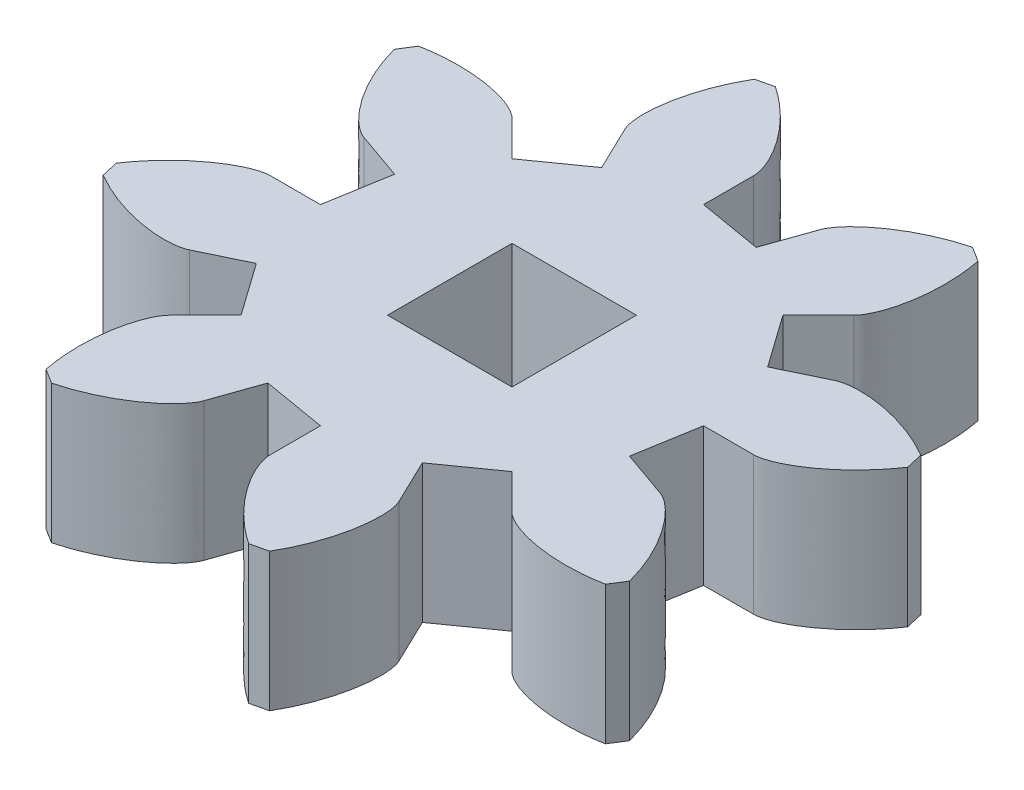
SolidWorks part; units mm, degrees
ref_plane "Front Plane" through (0, 0, 0) normal (0, 0, 1) x (1, 0, 0)
ref_plane "Top Plane" through (0, 0, 0) normal (0, 1, 0) x (1, 0, 0)
ref_plane "Right Plane" through (0, 0, 0) normal (1, 0, 0) x (0, 0, -1)
sketch "Sketch2" plane through (0, 0, 0) normal (0, 1, 0) x (1, 0, 0)
  circle A0 centre (0, 0) radius 5.8346 construction
  circle A1 centre (0, 0) radius 5.8346
sketch "Sketch3" plane through (0, 0, 0) normal (0, 1, 0) x (1, 0, 0)
  line L0 (4.157, 0) -> (5.2447, 0)
  line L1 (5.2447, 0) -> (5.2537, 0.0004)
  line L2 (5.2537, 0.0004) -> (5.2726, 0.002)
  line L3 (5.2726, 0.002) -> (5.3013, 0.0057)
  line L4 (5.3013, 0.0057) -> (5.3397, 0.0123)
  line L5 (5.3397, 0.0123) -> (5.3875, 0.0227)
  line L6 (5.3875, 0.0227) -> (5.4444, 0.0378)
  line L7 (5.4444, 0.0378) -> (5.5102, 0.0582)
  line L8 (5.5102, 0.0582) -> (5.5844, 0.0849)
  line L9 (5.5844, 0.0849) -> (5.6666, 0.1186)
  line L10 (5.6666, 0.1186) -> (5.7563, 0.16)
  line L11 (5.7563, 0.16) -> (5.8531, 0.2099)
  line L12 (5.8531, 0.2099) -> (5.9562, 0.2688)
  line L13 (5.9562, 0.2688) -> (6.0651, 0.3376)
  line L14 (6.0651, 0.3376) -> (6.1791, 0.4167)
  line L15 (6.1791, 0.4167) -> (6.2974, 0.5068)
  line L16 (6.2974, 0.5068) -> (6.4195, 0.6083)
  line L17 (6.4195, 0.6083) -> (6.5443, 0.7218)
  line L18 (6.5443, 0.7218) -> (6.6712, 0.8476)
  line L19 (6.6712, 0.8476) -> (6.7992, 0.9862)
  line L20 (6.7992, 0.9862) -> (6.9276, 1.1378)
  line L21 (6.9276, 1.1378) -> (7.0553, 1.3028)
  line L22 (7.0553, 1.3028) -> (7.1186, 1.3904)
  line L23 (7.1186, 1.3904) -> (7.1501, 1.4354)
  line L24 (7.1501, 1.4354) -> (7.1502, 1.4358)
  line L25 (7.1502, 1.4358) -> (7.0661, 1.8051)
  line L26 (7.0661, 1.8051) -> (7.0658, 1.8053)
  line L27 (7.0658, 1.8053) -> (7.0179, 1.8323)
  line L28 (7.0179, 1.8323) -> (6.9228, 1.8838)
  line L29 (6.9228, 1.8838) -> (6.7362, 1.9771)
  line L30 (6.7362, 1.9771) -> (6.5549, 2.0582)
  line L31 (6.5549, 2.0582) -> (6.3794, 2.1275)
  line L32 (6.3794, 2.1275) -> (6.2105, 2.1859)
  line L33 (6.2105, 2.1859) -> (6.0488, 2.2341)
  line L34 (6.0488, 2.2341) -> (5.8949, 2.2727)
  line L35 (5.8949, 2.2727) -> (5.7492, 2.3025)
  line L36 (5.7492, 2.3025) -> (5.6121, 2.3244)
  line L37 (5.6121, 2.3244) -> (5.4842, 2.3392)
  line L38 (5.4842, 2.3392) -> (5.3657, 2.3477)
  line L39 (5.3657, 2.3477) -> (5.2569, 2.3507)
  line L40 (5.2569, 2.3507) -> (5.1581, 2.3491)
  line L41 (5.1581, 2.3491) -> (5.0694, 2.3438)
  line L42 (5.0694, 2.3438) -> (4.991, 2.3357)
  line L43 (4.991, 2.3357) -> (4.9228, 2.3256)
  line L44 (4.9228, 2.3256) -> (4.865, 2.3145)
  line L45 (4.865, 2.3145) -> (4.8174, 2.3032)
  line L46 (4.8174, 2.3032) -> (4.78, 2.2925)
  line L47 (4.78, 2.2925) -> (4.7525, 2.2834)
  line L48 (4.7525, 2.2834) -> (4.7348, 2.2767)
  line L49 (4.7348, 2.2767) -> (4.7265, 2.2731)
  line L50 (4.7265, 2.2731) -> (3.7463, 1.8017)
  line L51 (3.7463, 1.8017) -> (2.9394, 2.9394)
  line L52 (2.9394, 2.9394) -> (3.7086, 3.7086)
  line L53 (3.7086, 3.7086) -> (3.7146, 3.7152)
  line L54 (3.7146, 3.7152) -> (3.7269, 3.7297)
  line L55 (3.7269, 3.7297) -> (3.7446, 3.7526)
  line L56 (3.7446, 3.7526) -> (3.767, 3.7844)
  line L57 (3.767, 3.7844) -> (3.7934, 3.8256)
  line L58 (3.7934, 3.8256) -> (3.8231, 3.8765)
  line L59 (3.8231, 3.8765) -> (3.8551, 3.9375)
  line L60 (3.8551, 3.9375) -> (3.8887, 4.0088)
  line L61 (3.8887, 4.0088) -> (3.923, 4.0908)
  line L62 (3.923, 4.0908) -> (3.9572, 4.1835)
  line L63 (3.9572, 4.1835) -> (3.9904, 4.2871)
  line L64 (3.9904, 4.2871) -> (4.0216, 4.4018)
  line L65 (4.0216, 4.4018) -> (4.05, 4.5274)
  line L66 (4.05, 4.5274) -> (4.0746, 4.6639)
  line L67 (4.0746, 4.6639) -> (4.0946, 4.8113)
  line L68 (4.0946, 4.8113) -> (4.1091, 4.9694)
  line L69 (4.1091, 4.9694) -> (4.1172, 5.1379)
  line L70 (4.1172, 5.1379) -> (4.1179, 5.3166)
  line L71 (4.1179, 5.3166) -> (4.1105, 5.5051)
  line L72 (4.1105, 5.5051) -> (4.094, 5.7031)
  line L73 (4.094, 5.7031) -> (4.0676, 5.9101)
  line L74 (4.0676, 5.9101) -> (4.0505, 6.0168)
  line L75 (4.0505, 6.0168) -> (4.0409, 6.0709)
  line L76 (4.0409, 6.0709) -> (4.0407, 6.0712)
  line L77 (4.0407, 6.0712) -> (3.7201, 6.2728)
  line L78 (3.7201, 6.2728) -> (3.7197, 6.2728)
  line L79 (3.7197, 6.2728) -> (3.6668, 6.258)
  line L80 (3.6668, 6.258) -> (3.5632, 6.2272)
  line L81 (3.5632, 6.2272) -> (3.3652, 6.1613)
  line L82 (3.3652, 6.1613) -> (3.1797, 6.0903)
  line L83 (3.1797, 6.0903) -> (3.0065, 6.0153)
  line L84 (3.0065, 6.0153) -> (2.8458, 5.9372)
  line L85 (2.8458, 5.9372) -> (2.6974, 5.8569)
  line L86 (2.6974, 5.8569) -> (2.5613, 5.7753)
  line L87 (2.5613, 5.7753) -> (2.4371, 5.6934)
  line L88 (2.4371, 5.6934) -> (2.3247, 5.612)
  line L89 (2.3247, 5.612) -> (2.2238, 5.532)
  line L90 (2.2238, 5.532) -> (2.1341, 5.4542)
  line L91 (2.1341, 5.4542) -> (2.055, 5.3794)
  line L92 (2.055, 5.3794) -> (1.9863, 5.3084)
  line L93 (1.9863, 5.3084) -> (1.9273, 5.242)
  line L94 (1.9273, 5.242) -> (1.8776, 5.1807)
  line L95 (1.8776, 5.1807) -> (1.8365, 5.1254)
  line L96 (1.8365, 5.1254) -> (1.8035, 5.0767)
  line L97 (1.8035, 5.0767) -> (1.7778, 5.035)
  line L98 (1.7778, 5.035) -> (1.7589, 5.001)
  line L99 (1.7589, 5.001) -> (1.7459, 4.9751)
  line L100 (1.7459, 4.9751) -> (1.7382, 4.9578)
  line L101 (1.7382, 4.9578) -> (1.7348, 4.9495)
  line L102 (1.7348, 4.9495) -> (1.375, 3.923)
  line L103 (1.375, 3.923) -> (0, 4.157)
  line L104 (0, 4.157) -> (0, 5.2447)
  line L105 (0, 5.2447) -> (-0.0004, 5.2537)
  line L106 (-0.0004, 5.2537) -> (-0.002, 5.2726)
  line L107 (-0.002, 5.2726) -> (-0.0057, 5.3013)
  line L108 (-0.0057, 5.3013) -> (-0.0123, 5.3397)
  line L109 (-0.0123, 5.3397) -> (-0.0227, 5.3875)
  line L110 (-0.0227, 5.3875) -> (-0.0378, 5.4444)
  line L111 (-0.0378, 5.4444) -> (-0.0582, 5.5102)
  line L112 (-0.0582, 5.5102) -> (-0.0849, 5.5844)
  line L113 (-0.0849, 5.5844) -> (-0.1186, 5.6666)
  line L114 (-0.1186, 5.6666) -> (-0.16, 5.7563)
  line L115 (-0.16, 5.7563) -> (-0.2099, 5.8531)
  line L116 (-0.2099, 5.8531) -> (-0.2688, 5.9562)
  line L117 (-0.2688, 5.9562) -> (-0.3376, 6.0651)
  line L118 (-0.3376, 6.0651) -> (-0.4167, 6.1791)
  line L119 (-0.4167, 6.1791) -> (-0.5068, 6.2974)
  line L120 (-0.5068, 6.2974) -> (-0.6083, 6.4195)
  line L121 (-0.6083, 6.4195) -> (-0.7218, 6.5443)
  line L122 (-0.7218, 6.5443) -> (-0.8476, 6.6712)
  line L123 (-0.8476, 6.6712) -> (-0.9862, 6.7992)
  line L124 (-0.9862, 6.7992) -> (-1.1378, 6.9276)
  line L125 (-1.1378, 6.9276) -> (-1.3028, 7.0553)
  line L126 (-1.3028, 7.0553) -> (-1.3904, 7.1186)
  line L127 (-1.3904, 7.1186) -> (-1.4354, 7.1501)
  line L128 (-1.4354, 7.1501) -> (-1.4358, 7.1502)
  line L129 (-1.4358, 7.1502) -> (-1.8051, 7.0661)
  line L130 (-1.8051, 7.0661) -> (-1.8053, 7.0658)
  line L131 (-1.8053, 7.0658) -> (-1.8323, 7.0179)
  line L132 (-1.8323, 7.0179) -> (-1.8838, 6.9228)
  line L133 (-1.8838, 6.9228) -> (-1.9771, 6.7362)
  line L134 (-1.9771, 6.7362) -> (-2.0582, 6.5549)
  line L135 (-2.0582, 6.5549) -> (-2.1275, 6.3794)
  line L136 (-2.1275, 6.3794) -> (-2.1859, 6.2105)
  line L137 (-2.1859, 6.2105) -> (-2.2341, 6.0488)
  line L138 (-2.2341, 6.0488) -> (-2.2727, 5.8949)
  line L139 (-2.2727, 5.8949) -> (-2.3025, 5.7492)
  line L140 (-2.3025, 5.7492) -> (-2.3244, 5.6121)
  line L141 (-2.3244, 5.6121) -> (-2.3392, 5.4842)
  line L142 (-2.3392, 5.4842) -> (-2.3477, 5.3657)
  line L143 (-2.3477, 5.3657) -> (-2.3507, 5.2569)
  line L144 (-2.3507, 5.2569) -> (-2.3491, 5.1581)
  line L145 (-2.3491, 5.1581) -> (-2.3438, 5.0694)
  line L146 (-2.3438, 5.0694) -> (-2.3357, 4.991)
  line L147 (-2.3357, 4.991) -> (-2.3256, 4.9228)
  line L148 (-2.3256, 4.9228) -> (-2.3145, 4.865)
  line L149 (-2.3145, 4.865) -> (-2.3032, 4.8174)
  line L150 (-2.3032, 4.8174) -> (-2.2925, 4.78)
  line L151 (-2.2925, 4.78) -> (-2.2834, 4.7525)
  line L152 (-2.2834, 4.7525) -> (-2.2767, 4.7348)
  line L153 (-2.2767, 4.7348) -> (-2.2731, 4.7265)
  line L154 (-2.2731, 4.7265) -> (-1.8017, 3.7463)
  line L155 (-1.8017, 3.7463) -> (-2.9394, 2.9394)
  line L156 (-2.9394, 2.9394) -> (-3.7086, 3.7086)
  line L157 (-3.7086, 3.7086) -> (-3.7152, 3.7146)
  line L158 (-3.7152, 3.7146) -> (-3.7297, 3.7269)
  line L159 (-3.7297, 3.7269) -> (-3.7526, 3.7446)
  line L160 (-3.7526, 3.7446) -> (-3.7844, 3.767)
  line L161 (-3.7844, 3.767) -> (-3.8256, 3.7934)
  line L162 (-3.8256, 3.7934) -> (-3.8765, 3.8231)
  line L163 (-3.8765, 3.8231) -> (-3.9375, 3.8551)
  line L164 (-3.9375, 3.8551) -> (-4.0088, 3.8887)
  line L165 (-4.0088, 3.8887) -> (-4.0908, 3.923)
  line L166 (-4.0908, 3.923) -> (-4.1835, 3.9572)
  line L167 (-4.1835, 3.9572) -> (-4.2871, 3.9904)
  line L168 (-4.2871, 3.9904) -> (-4.4018, 4.0216)
  line L169 (-4.4018, 4.0216) -> (-4.5274, 4.05)
  line L170 (-4.5274, 4.05) -> (-4.6639, 4.0746)
  line L171 (-4.6639, 4.0746) -> (-4.8113, 4.0946)
  line L172 (-4.8113, 4.0946) -> (-4.9694, 4.1091)
  line L173 (-4.9694, 4.1091) -> (-5.1379, 4.1172)
  line L174 (-5.1379, 4.1172) -> (-5.3166, 4.1179)
  line L175 (-5.3166, 4.1179) -> (-5.5051, 4.1105)
  line L176 (-5.5051, 4.1105) -> (-5.7031, 4.094)
  line L177 (-5.7031, 4.094) -> (-5.9101, 4.0676)
  line L178 (-5.9101, 4.0676) -> (-6.0168, 4.0505)
  line L179 (-6.0168, 4.0505) -> (-6.0709, 4.0409)
  line L180 (-6.0709, 4.0409) -> (-6.0712, 4.0407)
  line L181 (-6.0712, 4.0407) -> (-6.2728, 3.7201)
  line L182 (-6.2728, 3.7201) -> (-6.2728, 3.7197)
  line L183 (-6.2728, 3.7197) -> (-6.258, 3.6668)
  line L184 (-6.258, 3.6668) -> (-6.2272, 3.5632)
  line L185 (-6.2272, 3.5632) -> (-6.1613, 3.3652)
  line L186 (-6.1613, 3.3652) -> (-6.0903, 3.1797)
  line L187 (-6.0903, 3.1797) -> (-6.0153, 3.0065)
  line L188 (-6.0153, 3.0065) -> (-5.9372, 2.8458)
  line L189 (-5.9372, 2.8458) -> (-5.8569, 2.6974)
  line L190 (-5.8569, 2.6974) -> (-5.7753, 2.5613)
  line L191 (-5.7753, 2.5613) -> (-5.6934, 2.4371)
  line L192 (-5.6934, 2.4371) -> (-5.612, 2.3247)
  line L193 (-5.612, 2.3247) -> (-5.532, 2.2238)
  line L194 (-5.532, 2.2238) -> (-5.4542, 2.1341)
  line L195 (-5.4542, 2.1341) -> (-5.3794, 2.055)
  line L196 (-5.3794, 2.055) -> (-5.3084, 1.9863)
  line L197 (-5.3084, 1.9863) -> (-5.242, 1.9273)
  line L198 (-5.242, 1.9273) -> (-5.1807, 1.8776)
  line L199 (-5.1807, 1.8776) -> (-5.1254, 1.8365)
  line L200 (-5.1254, 1.8365) -> (-5.0767, 1.8035)
  line L201 (-5.0767, 1.8035) -> (-5.035, 1.7778)
  line L202 (-5.035, 1.7778) -> (-5.001, 1.7589)
  line L203 (-5.001, 1.7589) -> (-4.9751, 1.7459)
  line L204 (-4.9751, 1.7459) -> (-4.9578, 1.7382)
  line L205 (-4.9578, 1.7382) -> (-4.9495, 1.7348)
  line L206 (-4.9495, 1.7348) -> (-3.923, 1.375)
  line L207 (-3.923, 1.375) -> (-4.157, 0)
  line L208 (-4.157, 0) -> (-5.2447, 0)
  line L209 (-5.2447, 0) -> (-5.2537, -0.0004)
  line L210 (-5.2537, -0.0004) -> (-5.2726, -0.002)
  line L211 (-5.2726, -0.002) -> (-5.3013, -0.0057)
  line L212 (-5.3013, -0.0057) -> (-5.3397, -0.0123)
  line L213 (-5.3397, -0.0123) -> (-5.3875, -0.0227)
  line L214 (-5.3875, -0.0227) -> (-5.4444, -0.0378)
  line L215 (-5.4444, -0.0378) -> (-5.5102, -0.0582)
  line L216 (-5.5102, -0.0582) -> (-5.5844, -0.0849)
  line L217 (-5.5844, -0.0849) -> (-5.6666, -0.1186)
  line L218 (-5.6666, -0.1186) -> (-5.7563, -0.16)
  line L219 (-5.7563, -0.16) -> (-5.8531, -0.2099)
  line L220 (-5.8531, -0.2099) -> (-5.9562, -0.2688)
  line L221 (-5.9562, -0.2688) -> (-6.0651, -0.3376)
  line L222 (-6.0651, -0.3376) -> (-6.1791, -0.4167)
  line L223 (-6.1791, -0.4167) -> (-6.2974, -0.5068)
  line L224 (-6.2974, -0.5068) -> (-6.4195, -0.6083)
  line L225 (-6.4195, -0.6083) -> (-6.5443, -0.7218)
  line L226 (-6.5443, -0.7218) -> (-6.6712, -0.8476)
  line L227 (-6.6712, -0.8476) -> (-6.7992, -0.9862)
  line L228 (-6.7992, -0.9862) -> (-6.9276, -1.1378)
  line L229 (-6.9276, -1.1378) -> (-7.0553, -1.3028)
  line L230 (-7.0553, -1.3028) -> (-7.1186, -1.3904)
  line L231 (-7.1186, -1.3904) -> (-7.1501, -1.4354)
  line L232 (-7.1501, -1.4354) -> (-7.1502, -1.4358)
  line L233 (-7.1502, -1.4358) -> (-7.0661, -1.8051)
  line L234 (-7.0661, -1.8051) -> (-7.0658, -1.8053)
  line L235 (-7.0658, -1.8053) -> (-7.0179, -1.8323)
  line L236 (-7.0179, -1.8323) -> (-6.9228, -1.8838)
  line L237 (-6.9228, -1.8838) -> (-6.7362, -1.9771)
  line L238 (-6.7362, -1.9771) -> (-6.5549, -2.0582)
  line L239 (-6.5549, -2.0582) -> (-6.3794, -2.1275)
  line L240 (-6.3794, -2.1275) -> (-6.2105, -2.1859)
  line L241 (-6.2105, -2.1859) -> (-6.0488, -2.2341)
  line L242 (-6.0488, -2.2341) -> (-5.8949, -2.2727)
  line L243 (-5.8949, -2.2727) -> (-5.7492, -2.3025)
  line L244 (-5.7492, -2.3025) -> (-5.6121, -2.3244)
  line L245 (-5.6121, -2.3244) -> (-5.4842, -2.3392)
  line L246 (-5.4842, -2.3392) -> (-5.3657, -2.3477)
  line L247 (-5.3657, -2.3477) -> (-5.2569, -2.3507)
  line L248 (-5.2569, -2.3507) -> (-5.1581, -2.3491)
  line L249 (-5.1581, -2.3491) -> (-5.0694, -2.3438)
  line L250 (-5.0694, -2.3438) -> (-4.991, -2.3357)
  line L251 (-4.991, -2.3357) -> (-4.9228, -2.3256)
  line L252 (-4.9228, -2.3256) -> (-4.865, -2.3145)
  line L253 (-4.865, -2.3145) -> (-4.8174, -2.3032)
  line L254 (-4.8174, -2.3032) -> (-4.78, -2.2925)
  line L255 (-4.78, -2.2925) -> (-4.7525, -2.2834)
  line L256 (-4.7525, -2.2834) -> (-4.7348, -2.2767)
  line L257 (-4.7348, -2.2767) -> (-4.7265, -2.2731)
  line L258 (-4.7265, -2.2731) -> (-3.7463, -1.8017)
  line L259 (-3.7463, -1.8017) -> (-2.9394, -2.9394)
  line L260 (-2.9394, -2.9394) -> (-3.7086, -3.7086)
  line L261 (-3.7086, -3.7086) -> (-3.7146, -3.7152)
  line L262 (-3.7146, -3.7152) -> (-3.7269, -3.7297)
  line L263 (-3.7269, -3.7297) -> (-3.7446, -3.7526)
  line L264 (-3.7446, -3.7526) -> (-3.767, -3.7844)
  line L265 (-3.767, -3.7844) -> (-3.7934, -3.8256)
  line L266 (-3.7934, -3.8256) -> (-3.8231, -3.8765)
  line L267 (-3.8231, -3.8765) -> (-3.8551, -3.9375)
  line L268 (-3.8551, -3.9375) -> (-3.8887, -4.0088)
  line L269 (-3.8887, -4.0088) -> (-3.923, -4.0908)
  line L270 (-3.923, -4.0908) -> (-3.9572, -4.1835)
  line L271 (-3.9572, -4.1835) -> (-3.9904, -4.2871)
  line L272 (-3.9904, -4.2871) -> (-4.0216, -4.4018)
  line L273 (-4.0216, -4.4018) -> (-4.05, -4.5274)
  line L274 (-4.05, -4.5274) -> (-4.0746, -4.6639)
  line L275 (-4.0746, -4.6639) -> (-4.0946, -4.8113)
  line L276 (-4.0946, -4.8113) -> (-4.1091, -4.9694)
  line L277 (-4.1091, -4.9694) -> (-4.1172, -5.1379)
  line L278 (-4.1172, -5.1379) -> (-4.1179, -5.3166)
  line L279 (-4.1179, -5.3166) -> (-4.1105, -5.5051)
  line L280 (-4.1105, -5.5051) -> (-4.094, -5.7031)
  line L281 (-4.094, -5.7031) -> (-4.0676, -5.9101)
  line L282 (-4.0676, -5.9101) -> (-4.0505, -6.0168)
  line L283 (-4.0505, -6.0168) -> (-4.0409, -6.0709)
  line L284 (-4.0409, -6.0709) -> (-4.0407, -6.0712)
  line L285 (-4.0407, -6.0712) -> (-3.7201, -6.2728)
  line L286 (-3.7201, -6.2728) -> (-3.7197, -6.2728)
  line L287 (-3.7197, -6.2728) -> (-3.6668, -6.258)
  line L288 (-3.6668, -6.258) -> (-3.5632, -6.2272)
  line L289 (-3.5632, -6.2272) -> (-3.3652, -6.1613)
  line L290 (-3.3652, -6.1613) -> (-3.1797, -6.0903)
  line L291 (-3.1797, -6.0903) -> (-3.0065, -6.0153)
  line L292 (-3.0065, -6.0153) -> (-2.8458, -5.9372)
  line L293 (-2.8458, -5.9372) -> (-2.6974, -5.8569)
  line L294 (-2.6974, -5.8569) -> (-2.5613, -5.7753)
  line L295 (-2.5613, -5.7753) -> (-2.4371, -5.6934)
  line L296 (-2.4371, -5.6934) -> (-2.3247, -5.612)
  line L297 (-2.3247, -5.612) -> (-2.2238, -5.532)
  line L298 (-2.2238, -5.532) -> (-2.1341, -5.4542)
  line L299 (-2.1341, -5.4542) -> (-2.055, -5.3794)
  line L300 (-2.055, -5.3794) -> (-1.9863, -5.3084)
  line L301 (-1.9863, -5.3084) -> (-1.9273, -5.242)
  line L302 (-1.9273, -5.242) -> (-1.8776, -5.1807)
  line L303 (-1.8776, -5.1807) -> (-1.8365, -5.1254)
  line L304 (-1.8365, -5.1254) -> (-1.8035, -5.0767)
  line L305 (-1.8035, -5.0767) -> (-1.7778, -5.035)
  line L306 (-1.7778, -5.035) -> (-1.7589, -5.001)
  line L307 (-1.7589, -5.001) -> (-1.7459, -4.9751)
  line L308 (-1.7459, -4.9751) -> (-1.7382, -4.9578)
  line L309 (-1.7382, -4.9578) -> (-1.7348, -4.9495)
  line L310 (-1.7348, -4.9495) -> (-1.375, -3.923)
  line L311 (-1.375, -3.923) -> (0, -4.157)
  line L312 (0, -4.157) -> (0, -5.2447)
  line L313 (0, -5.2447) -> (0.0004, -5.2537)
  line L314 (0.0004, -5.2537) -> (0.002, -5.2726)
  line L315 (0.002, -5.2726) -> (0.0057, -5.3013)
  line L316 (0.0057, -5.3013) -> (0.0123, -5.3397)
  line L317 (0.0123, -5.3397) -> (0.0227, -5.3875)
  line L318 (0.0227, -5.3875) -> (0.0378, -5.4444)
  line L319 (0.0378, -5.4444) -> (0.0582, -5.5102)
  line L320 (0.0582, -5.5102) -> (0.0849, -5.5844)
  line L321 (0.0849, -5.5844) -> (0.1186, -5.6666)
  line L322 (0.1186, -5.6666) -> (0.16, -5.7563)
  line L323 (0.16, -5.7563) -> (0.2099, -5.8531)
  line L324 (0.2099, -5.8531) -> (0.2688, -5.9562)
  line L325 (0.2688, -5.9562) -> (0.3376, -6.0651)
  line L326 (0.3376, -6.0651) -> (0.4167, -6.1791)
  line L327 (0.4167, -6.1791) -> (0.5068, -6.2974)
  line L328 (0.5068, -6.2974) -> (0.6083, -6.4195)
  line L329 (0.6083, -6.4195) -> (0.7218, -6.5443)
  line L330 (0.7218, -6.5443) -> (0.8476, -6.6712)
  line L331 (0.8476, -6.6712) -> (0.9862, -6.7992)
  line L332 (0.9862, -6.7992) -> (1.1378, -6.9276)
  line L333 (1.1378, -6.9276) -> (1.3028, -7.0553)
  line L334 (1.3028, -7.0553) -> (1.3904, -7.1186)
  line L335 (1.3904, -7.1186) -> (1.4354, -7.1501)
  line L336 (1.4354, -7.1501) -> (1.4358, -7.1502)
  line L337 (1.4358, -7.1502) -> (1.8051, -7.0661)
  line L338 (1.8051, -7.0661) -> (1.8053, -7.0658)
  line L339 (1.8053, -7.0658) -> (1.8323, -7.0179)
  line L340 (1.8323, -7.0179) -> (1.8838, -6.9228)
  line L341 (1.8838, -6.9228) -> (1.9771, -6.7362)
  line L342 (1.9771, -6.7362) -> (2.0582, -6.5549)
  line L343 (2.0582, -6.5549) -> (2.1275, -6.3794)
  line L344 (2.1275, -6.3794) -> (2.1859, -6.2105)
  line L345 (2.1859, -6.2105) -> (2.2341, -6.0488)
  line L346 (2.2341, -6.0488) -> (2.2727, -5.8949)
  line L347 (2.2727, -5.8949) -> (2.3025, -5.7492)
  line L348 (2.3025, -5.7492) -> (2.3244, -5.6121)
  line L349 (2.3244, -5.6121) -> (2.3392, -5.4842)
  line L350 (2.3392, -5.4842) -> (2.3477, -5.3657)
  line L351 (2.3477, -5.3657) -> (2.3507, -5.2569)
  line L352 (2.3507, -5.2569) -> (2.3491, -5.1581)
  line L353 (2.3491, -5.1581) -> (2.3438, -5.0694)
  line L354 (2.3438, -5.0694) -> (2.3357, -4.991)
  line L355 (2.3357, -4.991) -> (2.3256, -4.9228)
  line L356 (2.3256, -4.9228) -> (2.3145, -4.865)
  line L357 (2.3145, -4.865) -> (2.3032, -4.8174)
  line L358 (2.3032, -4.8174) -> (2.2925, -4.78)
  line L359 (2.2925, -4.78) -> (2.2834, -4.7525)
  line L360 (2.2834, -4.7525) -> (2.2767, -4.7348)
  line L361 (2.2767, -4.7348) -> (2.2731, -4.7265)
  line L362 (2.2731, -4.7265) -> (1.8017, -3.7463)
  line L363 (1.8017, -3.7463) -> (2.9394, -2.9394)
  line L364 (2.9394, -2.9394) -> (3.7086, -3.7086)
  line L365 (3.7086, -3.7086) -> (3.7152, -3.7146)
  line L366 (3.7152, -3.7146) -> (3.7297, -3.7269)
  line L367 (3.7297, -3.7269) -> (3.7526, -3.7446)
  line L368 (3.7526, -3.7446) -> (3.7844, -3.767)
  line L369 (3.7844, -3.767) -> (3.8256, -3.7934)
  line L370 (3.8256, -3.7934) -> (3.8765, -3.8231)
  line L371 (3.8765, -3.8231) -> (3.9375, -3.8551)
  line L372 (3.9375, -3.8551) -> (4.0088, -3.8887)
  line L373 (4.0088, -3.8887) -> (4.0908, -3.923)
  line L374 (4.0908, -3.923) -> (4.1835, -3.9572)
  line L375 (4.1835, -3.9572) -> (4.2871, -3.9904)
  line L376 (4.2871, -3.9904) -> (4.4018, -4.0216)
  line L377 (4.4018, -4.0216) -> (4.5274, -4.05)
  line L378 (4.5274, -4.05) -> (4.6639, -4.0746)
  line L379 (4.6639, -4.0746) -> (4.8113, -4.0946)
  line L380 (4.8113, -4.0946) -> (4.9694, -4.1091)
  line L381 (4.9694, -4.1091) -> (5.1379, -4.1172)
  line L382 (5.1379, -4.1172) -> (5.3166, -4.1179)
  line L383 (5.3166, -4.1179) -> (5.5051, -4.1105)
  line L384 (5.5051, -4.1105) -> (5.7031, -4.094)
  line L385 (5.7031, -4.094) -> (5.9101, -4.0676)
  line L386 (5.9101, -4.0676) -> (6.0168, -4.0505)
  line L387 (6.0168, -4.0505) -> (6.0709, -4.0409)
  line L388 (6.0709, -4.0409) -> (6.0712, -4.0407)
  line L389 (6.0712, -4.0407) -> (6.2728, -3.7201)
  line L390 (6.2728, -3.7201) -> (6.2728, -3.7197)
  line L391 (6.2728, -3.7197) -> (6.258, -3.6668)
  line L392 (6.258, -3.6668) -> (6.2272, -3.5632)
  line L393 (6.2272, -3.5632) -> (6.1613, -3.3652)
  line L394 (6.1613, -3.3652) -> (6.0903, -3.1797)
  line L395 (6.0903, -3.1797) -> (6.0153, -3.0065)
  line L396 (6.0153, -3.0065) -> (5.9372, -2.8458)
  line L397 (5.9372, -2.8458) -> (5.8569, -2.6974)
  line L398 (5.8569, -2.6974) -> (5.7753, -2.5613)
  line L399 (5.7753, -2.5613) -> (5.6934, -2.4371)
  line L400 (5.6934, -2.4371) -> (5.612, -2.3247)
  line L401 (5.612, -2.3247) -> (5.532, -2.2238)
  line L402 (5.532, -2.2238) -> (5.4542, -2.1341)
  line L403 (5.4542, -2.1341) -> (5.3794, -2.055)
  line L404 (5.3794, -2.055) -> (5.3084, -1.9863)
  line L405 (5.3084, -1.9863) -> (5.242, -1.9273)
  line L406 (5.242, -1.9273) -> (5.1807, -1.8776)
  line L407 (5.1807, -1.8776) -> (5.1254, -1.8365)
  line L408 (5.1254, -1.8365) -> (5.0767, -1.8035)
  line L409 (5.0767, -1.8035) -> (5.035, -1.7778)
  line L410 (5.035, -1.7778) -> (5.001, -1.7589)
  line L411 (5.001, -1.7589) -> (4.9751, -1.7459)
  line L412 (4.9751, -1.7459) -> (4.9578, -1.7382)
  line L413 (4.9578, -1.7382) -> (4.9495, -1.7348)
  line L414 (4.9495, -1.7348) -> (3.923, -1.375)
  line L415 (3.923, -1.375) -> (4.157, 0)
  circle A0 centre (5.6884, 1.2968) radius 0.5725 construction
  circle A1 centre (0, 0) radius 5.8344 construction
  circle A2 centre (0, 0) radius 7.293 construction
  circle A3 centre (0, 0) radius 5.2439 construction
sketch "Sketch5" plane through (0, 0, 0) normal (0, 1, 0) x (1, 0, 0)
  line L0 (0, 0) -> (7.1082, 1.6204) construction
  line L1 (7.1502, 1.4358) -> (7.0661, 1.8051) construction
  line L2 (0, 0) -> (3.3429, 2.3706)
  line L3 (3.7463, 1.8017) -> (2.9394, 2.9394) construction
  line L4 (3.3429, 2.3706) -> (3.7463, 1.8017)
  line L5 (3.7463, 1.8017) -> (4.7265, 2.2731)
  line L6 (7.0661, 1.8051) -> (7.1082, 1.6204)
  line L7 (4.157, 0) -> (5.2447, 0)
  line L8 (4.04, -0.6875) -> (4.157, 0)
  line L9 (0, 0) -> (4.04, -0.6875)
  line L10 (7.1502, 1.4358) -> (7.1082, 1.6204)
  spline S0 degree 3 poles (4.7265, 2.2731) (5.0838, 2.445) (6.115, 2.3613) (7.0661, 1.8051) knots 0 0 0 0 1 1 1 1
  spline S1 degree 3 poles (5.2447, 0) (5.6412, 0) (6.5342, 0.5224) (7.1502, 1.4358) knots 0 0 0 0 1 1 1 1
  dimension "D1" = 22.5
extrude "Boss-Extrude1" add sketch "Sketch5" along normal blind 1.5 and the other way blind 1.5
pattern_circular "CirPattern1" count 8 over 360 about axis through (0, -1.5, 0) along (0, 1, 0) of "Boss-Extrude1"
sketch "Sketch4" plane through (0, 1.5, 0) normal (0, 1, 0) x (1, 0, 0)
  line L1 (-1.35, 1.35) -> (1.35, 1.35)
  line L2 (-1.35, 1.35) -> (-1.35, -1.35)
  line L3 (-1.35, -1.35) -> (1.35, -1.35)
  line L4 (1.35, 1.35) -> (1.35, -1.35)
  line L5 (0, -1.35) -> (0, 1.35) construction
  line L6 (-1.35, 0) -> (1.35, 0) construction
  point P0 (0, 0)
  dimension "D1" = 2.7
extrude "Cut-Extrude1" cut sketch "Sketch4" against normal through all
